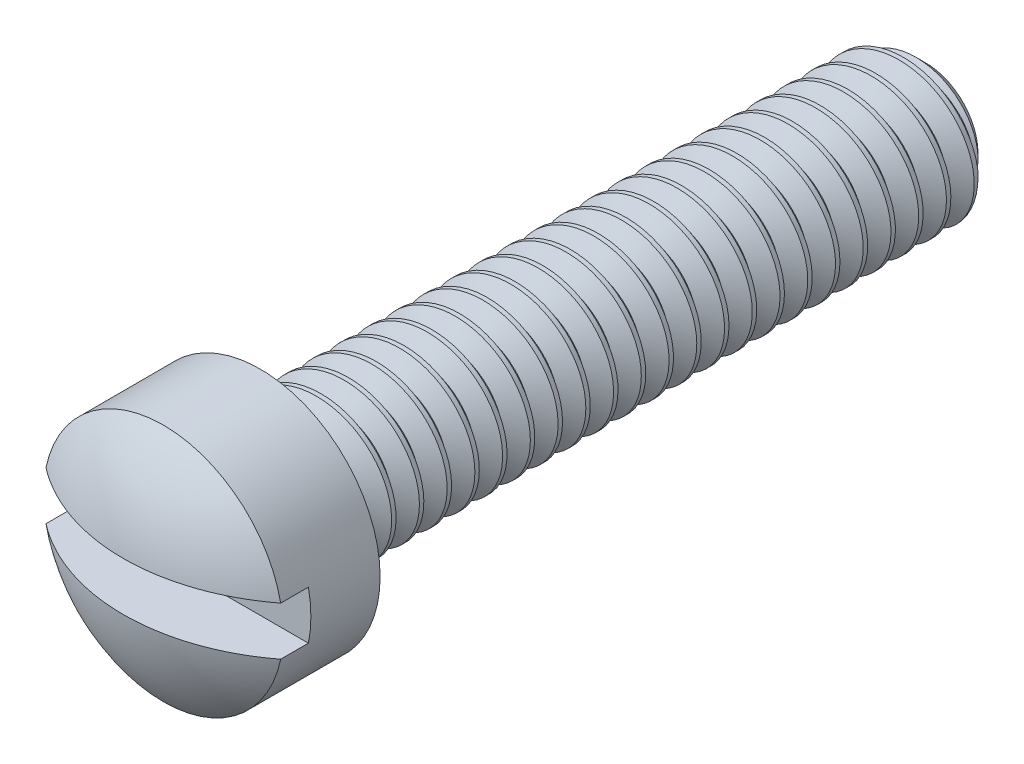
SolidWorks part; units mm, degrees
material "Cast Alloy Steel"
ref_plane "Front" through (0, 0, 0) normal (0, 0, 1) x (1, 0, 0)
ref_plane "Top" through (0, 0, 0) normal (0, 1, 0) x (1, 0, 0)
ref_plane "Right" through (0, 0, 0) normal (1, 0, 0) x (0, 0, -1)
sketch "Sketch1" plane through (0, 0, 0) normal (0, 0, 1) x (1, 0, 0)
  circle A0 centre (0, 0) radius 3.429
  dimension "Head Dia" = 6.858
extrude "Extrude3" add sketch "Sketch1" along normal blind 3.9624
sketch "Sketch11" plane through (0, 0, 0) normal (1, 0, 0) x (0, 0, -1)
  line L0 (0, 0) -> (-4.2164, 0) construction
  line L4 (-3.9624, 3.429) -> (-3.9624, -3.429) construction
  line L5 (-4.2164, 3.5662) -> (0, 3.5662)
  line L7 (0, 3.5662) -> (0, 3.429)
  line L8 (-2.7737, 3.429) -> (0, 3.429)
  line L9 (0, -3.429) -> (0, 3.429) construction
  line L13 (-3.9624, 0) -> (-4.2164, 0)
  line L14 (-4.2164, 0) -> (-4.2164, 3.5662)
  arc A0 (-2.7737, 3.429) -> (-3.9624, 0) centre (1.5776, 0) ccw
  dimension "D2" = 1.1887
  dimension "D3" = 0.254
  dimension "D5" = 0.1372
revolve "Cut-Revolve3" cut sketch "Sketch11" angle 360 about L0
sketch "Sketch4" plane through (0, 0, 0) normal (1, 0, 0) x (0, 0, -1)
  line L0 (0, 0) -> (19.05, 0)
  line L3 (19.05, 0) -> (19.05, 2.0828)
  line L4 (19.05, 2.0828) -> (0, 2.0828)
  line L6 (0, 2.0828) -> (0, 0)
  line L9 (19.05, 2.0828) -> (19.05, -2.0828) construction
  dimension "dia" = 4.1656
  dimension "length" = 19.05
revolve "Revolve1" add sketch "Sketch4" angle 360 about L0
sketch "Sketch13" plane through (0, 0, -19.05) normal (0, 0, -1) x (-1, 0, 0)
  circle A2 centre (0, 0) radius 2.0828
curve "Helix/Spiral1" pitch 0.7937 height 23.0124 turns 28.992
chamfer "Chamfer2" distance 0.5953 angle 45 1 edges at (2.0828, 0, -19.05)
sketch "Sketch14" plane through (0, 0, 0) normal (1, 0, 0) x (0, 0, -1)
  line L0 (19.05, 2.1076) -> (19.7445, 2.1076)
  line L1 (19.7445, 2.1076) -> (19.4469, 1.5706)
  line L2 (19.4469, 1.5706) -> (19.3477, 1.5706)
  line L3 (19.3477, 1.5706) -> (19.05, 2.1076)
  line L4 (19.1988, 1.8391) -> (19.5957, 1.8391) construction
  dimension "D1" = 0.0992
  dimension "D2" = 58
  dimension "D3" = 0.3969
  dimension "D4" = 0.0248
sweep "Cut-Sweep1" cut profiles "Sketch14" path "Helix/Spiral1"
ref_plane "Plane1" through (0, 0, 19.05) normal (0, 0, -1) x (-1, 0, 0)
sketch "Sketch29" [suppressed] plane through (0, 0, 28.575) normal (0, 0, -1) x (-1, 0, 0)
  circle A0 centre (0, 0) radius 1.7526 construction
  circle A1 centre (0, 0) radius 1.7526
  point P3 (0, -1.7526)
  point P4 (0, 1.7526)
extrude "Extrude11" [suppressed] add sketch "Sketch29" against normal up to surface (28.575 mm away)
ref_plane "Plane2" through (0, 0, 3.9624) normal (0, 0, 1) x (1, 0, 0)
sketch "Sketch26" plane through (0, 0, 0) normal (0, 0, 1) x (1, 0, 0)
  circle A1 centre (0, 0) radius 0.5461
  dimension "D1" = 1.0922
extrude "Extrude13" add sketch "Sketch26" along normal up to surface (3.9354 mm away)
sketch "Sketch31" plane through (0, 0, 3.9624) normal (0, 0, 1) x (1, 0, 0)
  line L0 (-3.429, 0.6945) -> (3.429, -0.6945) construction
  line L1 (-3.429, 0.6945) -> (3.429, 0.6945)
  line L2 (-3.429, 0.6945) -> (-3.429, -0.6945)
  line L3 (-3.429, -0.6945) -> (3.429, -0.6945)
  line L4 (3.429, 0.6945) -> (3.429, -0.6945)
  circle A0 centre (0, 0) radius 3.429 construction
  dimension "D1" = 1.3891
extrude "Extrude15" cut sketch "Sketch31" against normal blind 1.9812
sketch "Sketch18" plane through (0, 0, 0) normal (1, 0, 0) x (0, 0, -1)
  line L1 (19.05, 2.0828) -> (0, 2.0828) construction
  point P0 (17.8594, -2.0828)
  point P1 (18.2563, 2.0828)
  point P2 (-3.9624, 0.6945)
  dimension "D1" = 0.7937
  dimension "D2" = 1.1906
equation "\"D3@Helix/Spiral1\" = \"Length@Sketch4\" + \"Head Ht@Extrude3\""
equation "\"D1@Sketch14\" = \"D4@Helix/Spiral1\" * .125"
equation "\"D3@Sketch14\" = \"D4@Helix/Spiral1\" * .5"
equation "\"D5@Sketch11\" = \"Head Dia@Sketch1\" * .02"
equation "\"D4@Sketch14\" = \"D1@Sketch14\" * .25"
equation "\"D1@Chamfer2\" = \"D4@Helix/Spiral1\" * .75"
equation "\"D1@Sketch18\" = \"D4@Helix/Spiral1\""
equation "\"D2@Sketch18\" = \"D4@Helix/Spiral1\" * 1.5"
equation "\"D1@Extrude15\" = \"Head Ht@Extrude3\" * .5"
equation "\"D2@Sketch11\" = \"Head Ht@Extrude3\" * .3"
equation "\"D1@Sketch31\" = \"D4@Helix/Spiral1\" * 1.75"
